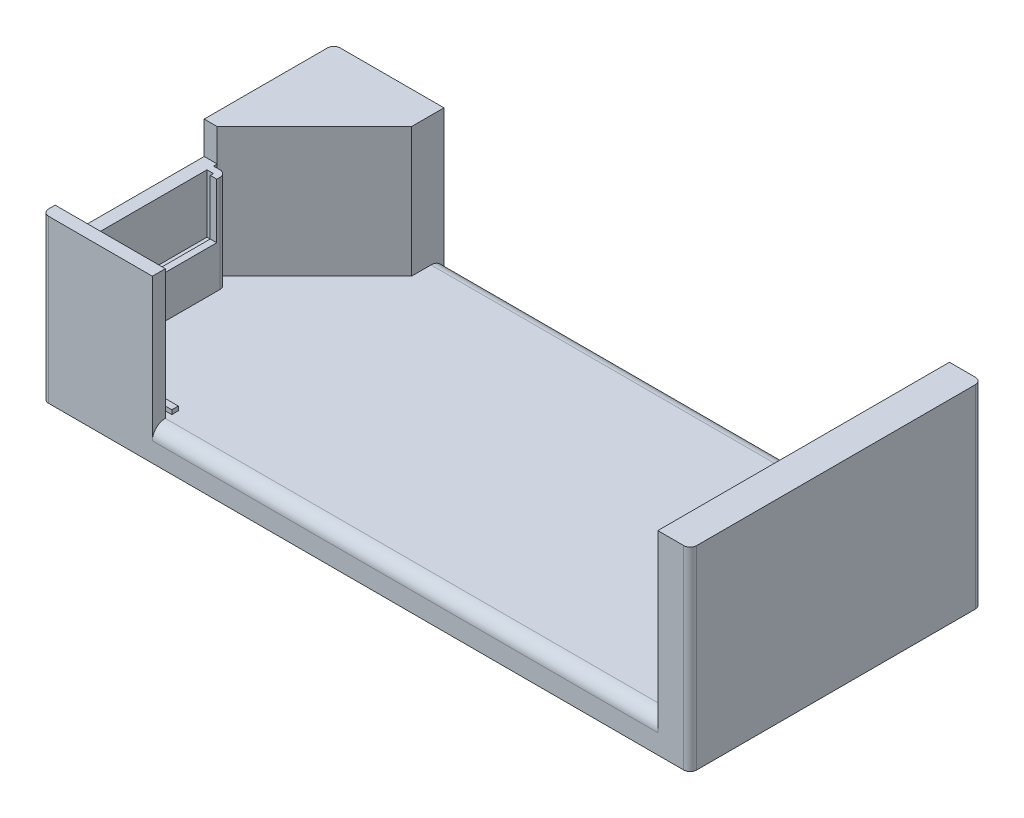
SolidWorks part; units mm, degrees
ref_plane "Front Plane" through (0, 0, 0) normal (0, 0, 1) x (1, 0, 0)
ref_plane "Top Plane" through (0, 0, 0) normal (0, 1, 0) x (1, 0, 0)
ref_plane "Right Plane" through (0, 0, 0) normal (1, 0, 0) x (0, 0, -1)
sketch "Sketch1" plane through (0, 0, 0) normal (0, 1, 0) x (1, 0, 0)
  line L0 (-48, -22.5) -> (-48, 2.5)
  line L1 (-50, -22.5) -> (50, -22.5)
  line L2 (-50, -22.5) -> (-50, 22.5)
  line L3 (-50, 22.5) -> (50, 22.5)
  line L4 (50, -22.5) -> (50, 22.5)
  line L5 (-50, -22.5) -> (50, 22.5) construction
  line L6 (-50, 22.5) -> (50, -22.5) construction
  line L7 (50, -22.5) -> (45, -22.5)
  line L8 (50, -22.5) -> (50, 22.5)
  line L9 (50, 22.5) -> (45, 22.5)
  line L10 (45, -22.5) -> (45, 22.5)
  line L11 (50, -22.5) -> (45, 22.5) construction
  line L12 (50, 22.5) -> (45, -22.5) construction
  line L13 (-48, 2.5) -> (-28, 22.5)
  line L14 (-48, -20.5) -> (-33, -20.5)
  line L15 (-33, -20.5) -> (-33, -22.5)
  line L16 (-33, 17.5) -> (-33, 22.5)
  line L17 (-48, -20.5) -> (-50, -20.5)
  line L18 (-48, 2.5) -> (-50, 2.5)
  line L20 (-48, -19.5) -> (-33, -19.5)
  line L21 (-48, -19.5) -> (-48, -18.5)
  line L22 (-48, -18.5) -> (-33, -18.5)
  line L23 (-33, -19.5) -> (-33, -18.5)
  line L24 (-48, -19.5) -> (-33, -18.5) construction
  line L25 (-48, -18.5) -> (-33, -19.5) construction
  point P0 (0, 0)
  point P8 (47.5, 0)
  point P23 (-40.5, -19)
  dimension "D1" = 100
  dimension "D2" = 45
  dimension "D3" = 5
  dimension "D4" = 135
  dimension "D5" = 2
  dimension "D6" = 15
  dimension "10" = 20
  dimension "D7" = 15
  dimension "D8" = 2
  dimension "D9" = 1
  dimension "D10" = 1
extrude "Boss-Extrude1" add sketch "Sketch1" against normal blind 5 contours L18 L13 L16 L3 L2 | L14 L15 L1 L10 L3 L13 L0 | L16 L13 L3 | L10 L1 L4 L3 | L0 L18 L2 L17 | L15 L14 L0 L1 | L0 L17 L2 L1 | L20 L23 L22 L0 region at (-49, 0, 21.5) region at (-40.5, 0, 21.5) region at (-49, 0, 9) region at (0.9674, 0, 0.5677) region at (-40.5, 0, 19) region at (47.5, 0, 0) region at (-43.2308, 0, -14.9725) region at (-31.3333, 0, -20.8333)
extrude "Boss-Extrude2" add sketch "Sketch1<4>" along normal blind 25 contours L10 L1 L4 L3 region at (47.5, 0, 0)
sketch "Sketch1<4>" plane through (0, 0, 0) normal (0, 1, 0) x (1, 0, 0) same geometry as "Sketch1"
extrude "Boss-Extrude3" add sketch "Sketch1<5>" along normal blind 20 contours L15 L14 L0 L1 | L0 L17 L2 L1 region at (-49, 0, 21.5) region at (-40.5, 0, 21.5)
sketch "Sketch1<5>" plane through (0, 0, 0) normal (0, 1, 0) x (1, 0, 0) same geometry as "Sketch1"
extrude "Boss-Extrude4" add sketch "Sketch1<6>" along normal blind 20 contours L18 L13 L16 L3 L2 region at (-43.2308, 0, -14.9725)
sketch "Sketch1<6>" plane through (0, 0, 0) normal (0, 1, 0) x (1, 0, 0) same geometry as "Sketch1"
extrude "Boss-Extrude5" add sketch "Sketch1<8>" along normal blind 15 contours L0 L18 L2 L17 region at (-49, 0, 9)
sketch "Sketch1<8>" plane through (0, 0, 0) normal (0, 1, 0) x (1, 0, 0) same geometry as "Sketch1"
extrude "Boss-Extrude6" add sketch "Sketch1<9>" along normal blind 0.65 from surface contours L20 L23 L22 L0 region at (-40.5, 0, 19) starting at face at (-17.25, 0, 2.625)
sketch "Sketch1<9>" plane through (0, 0, 0) normal (0, 1, 0) x (1, 0, 0) same geometry as "Sketch1"
sketch "Sketch4" plane through (0, 0, 20.5) normal (0, 0, -1) x (-1, 0, 0)
  line L0 (33, 20) -> (33, 0) construction
  line L1 (42, 0) -> (43.5, 0)
  line L2 (42, 0) -> (42, 15)
  line L3 (42, 15) -> (43.5, 15)
  line L4 (43.5, 0) -> (43.5, 15)
  line L5 (42, 0) -> (43.5, 15) construction
  line L6 (42, 15) -> (43.5, 0) construction
  line L7 (50, 0) -> (-50, 0) construction
  line L9 (42, 15) -> (41.5, 15)
  line L10 (42, 15) -> (42, 0)
  line L11 (42, 0) -> (41.5, 0)
  line L12 (41.5, 15) -> (41.5, 0)
  line L13 (42, 15) -> (41.5, 0) construction
  line L14 (42, 0) -> (41.5, 15) construction
  point P4 (42.75, 7.5)
  point P9 (42.75, 15)
  point P12 (41.75, 7.5)
  line M5 (33, 0) -> (48, 0)
  dimension "D1" = 9
  dimension "D2" = 1.5
  dimension "D3" = 15
  dimension "D4" = 0.5
extrude "Boss-Extrude7" add sketch "Sketch4" along normal blind 1 contours L4 L3 L2 M5 region at (-42.75, 7.5, 20.5)
extrude "Boss-Extrude8" add sketch "Sketch4<4>" along normal blind 1 from surface contours L9 L12 L2 M5 | L4 L3 L2 M5 region at (-42.75, 7.5, 20.5) region at (-41.75, 7.5, 20.5) starting at face at (-42.75, 7.825, 19.5)
sketch "Sketch4<4>" plane through (0, 0, 20.5) normal (0, 0, -1) x (-1, 0, 0) same geometry as "Sketch4"
sketch "Sketch5" plane through (-48, 0, 0) normal (1, 0, 0) x (0, 0, -1)
  line L0 (-20.5, 15) -> (2.5, 15) construction
  line L1 (-17.3162, 15) -> (0.9338, 15)
  line L2 (-17.3162, 15) -> (-17.3162, 6)
  line L3 (-17.3162, 6) -> (0.9338, 6)
  line L4 (0.9338, 15) -> (0.9338, 6)
  line L5 (-17.3162, 15) -> (0.9338, 6) construction
  line L6 (-17.3162, 6) -> (0.9338, 15) construction
  line L7 (-18.5, 0) -> (2.5, 0) construction
  line L8 (-17.3162, 15) -> (-18.3162, 15)
  line L9 (-17.3162, 15) -> (-17.3162, 6)
  line L10 (-17.3162, 6) -> (-18.3162, 6)
  line L11 (-18.3162, 15) -> (-18.3162, 6)
  line L12 (-17.3162, 15) -> (-18.3162, 6) construction
  line L13 (-17.3162, 6) -> (-18.3162, 15) construction
  line L14 (-18.3162, 6) -> (1.9338, 6)
  line L15 (-18.3162, 6) -> (-18.3162, 0)
  line L16 (-18.3162, 0) -> (1.9338, 0)
  line L17 (1.9338, 6) -> (1.9338, 0)
  line L18 (-18.3162, 6) -> (1.9338, 0) construction
  line L19 (-18.3162, 0) -> (1.9338, 6) construction
  line L20 (1.9338, 6) -> (0.9338, 6)
  line L21 (1.9338, 6) -> (1.9338, 15)
  line L22 (1.9338, 15) -> (0.9338, 15)
  line L23 (0.9338, 6) -> (0.9338, 15)
  line L24 (1.9338, 6) -> (0.9338, 15) construction
  line L25 (1.9338, 15) -> (0.9338, 6) construction
  line L27 (-17.3162, 6) -> (-16.8162, 6)
  line L28 (-17.3162, 6) -> (-17.3162, 15)
  line L29 (-17.3162, 15) -> (-16.8162, 15)
  line L30 (-16.8162, 6) -> (-16.8162, 15)
  line L31 (-17.3162, 6) -> (-16.8162, 15) construction
  line L32 (-17.3162, 15) -> (-16.8162, 6) construction
  line L33 (0.4338, 6) -> (0.9338, 6)
  line L34 (0.4338, 6) -> (0.4338, 15)
  line L35 (0.4338, 15) -> (0.9338, 15)
  line L36 (0.9338, 6) -> (0.9338, 15)
  line L37 (0.4338, 6) -> (0.9338, 15) construction
  line L38 (0.4338, 15) -> (0.9338, 6) construction
  line L39 (-18.3162, 6) -> (0.9338, 6)
  line L40 (-18.3162, 6) -> (-18.3162, 6.5)
  line L41 (-18.3162, 6.5) -> (0.9338, 6.5)
  line L42 (0.9338, 6) -> (0.9338, 6.5)
  line L43 (-18.3162, 6) -> (0.9338, 6.5) construction
  line L44 (-18.3162, 6.5) -> (0.9338, 6) construction
  point P4 (-8.1912, 10.5)
  point P11 (-17.8162, 10.5)
  point P13 (-8.1912, 3)
  point P16 (1.4338, 10.5)
  point P20 (-17.0662, 10.5)
  point P24 (0.6838, 10.5)
  point P26 (-8.6912, 6.25)
  line M7 (-18.5, 0) -> (2.5, 0)
  line M9 (2.5, 15) -> (-20.5, 15)
  dimension "D1" = 9
  dimension "D2" = 18.25
  dimension "D3" = 1
  dimension "D4" = 1
  dimension "D5" = 0.5
  dimension "D6" = 0.5
  dimension "D7" = 0.5
extrude "Boss-Extrude9" add sketch "Sketch5" along normal blind 1 contours L17 L14 L3 L10 L15 M7 | L11 L41 L2 M9 | L41 L11 L10 L28 | L14 L21 L4 L36 M9 region at (-48, 10.75, 17.8162) region at (-48, 6.25, 17.8162) region at (-48, 3, 8.1912) region at (-48, 10.5, -1.4338)
extrude "Boss-Extrude11" add sketch "Sketch5<5>" along normal blind 1 from surface contours L11 L41 L2 M9 | L2 L41 L30 L1 | L41 L11 L10 L28 | L41 L28 L3 L30 | L17 L14 L3 L10 L15 M7 | L41 L30 L14 L34 | L34 L41 L4 M9 | L41 L34 L3 L36 | L14 L21 L4 L36 M9 region at (-48, 10.75, 17.0662) region at (-48, 10.75, 17.8162) region at (-48, 6.25, 17.0662) region at (-48, 6.25, 17.8162) region at (-48, 10.75, -0.6838) region at (-48, 6.25, 8.1912) region at (-48, 3, 8.1912) region at (-48, 10.5, -1.4338) region at (-48, 6.25, -0.6838) starting at face at (-47, 9, 8.1912)
sketch "Sketch5<5>" plane through (-48, 0, 0) normal (1, 0, 0) x (0, 0, -1) same geometry as "Sketch5"
fillet "Fillet1" radius 1 3 edges at (-46, 7.5, -1.9338) (-43.5, 7.825, 18.5) (-46, 7.5, 18.3162)
fillet "Fillet2" radius 1 4 edges at (50, 10, 22.5) (-50, 7.5, 22.5) (50, 10, -22.5) (-50, 7.5, -22.5)
fillet "Fillet3" radius 2 2 edges at (6, 0, 22.5) (6, 0, -22.5)
